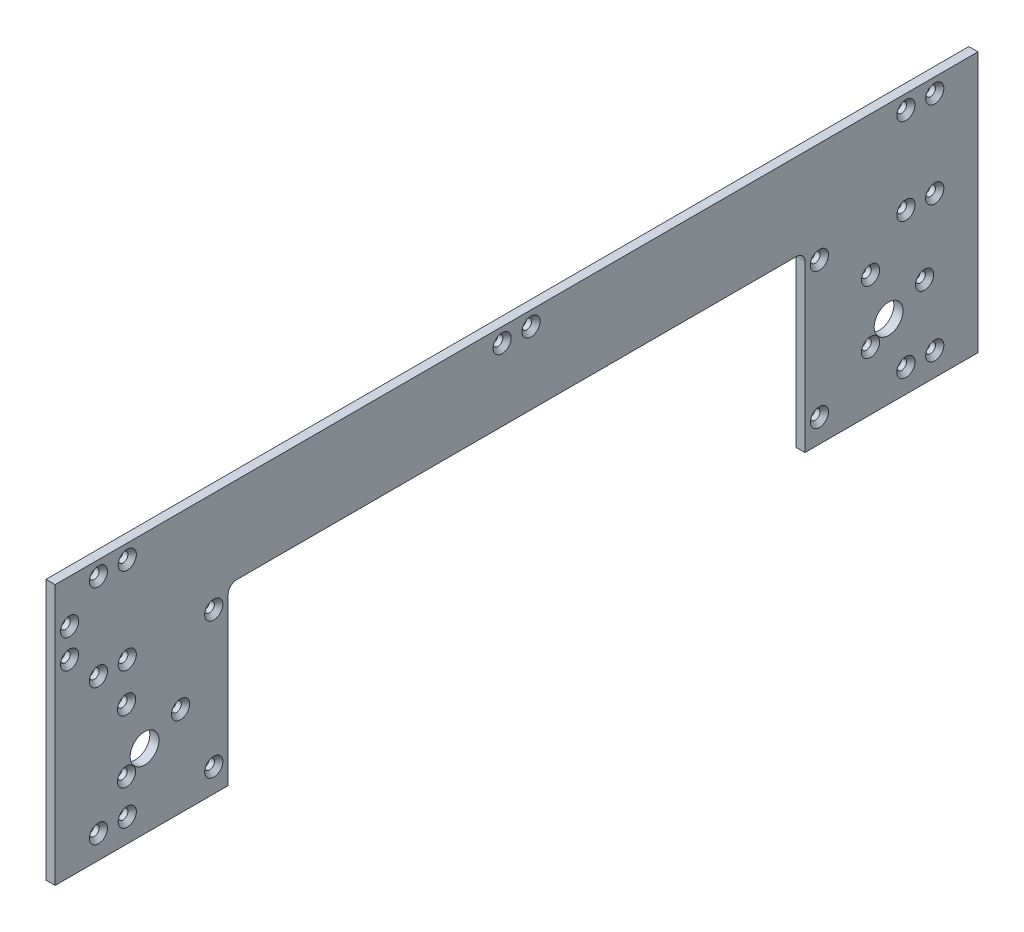
SolidWorks part; units mm, degrees
material "Garolite (G-10/FR4)"
ref_plane "Front Plane" through (0, 0, 0) normal (0, 0, 1) x (1, 0, 0)
ref_plane "Top Plane" through (0, 0, 0) normal (0, 1, 0) x (1, 0, 0)
ref_plane "Right Plane" through (0, 0, 0) normal (1, 0, 0) x (0, 0, -1)
sketch "Sketch1" plane through (0, 0, 0) normal (1, 0, 0) x (0, 0, -1)
  line L0 (160, 0) -> (160, 3.175)
  line L1 (-160, 0) -> (160, 0)
  line L2 (160, 3.175) -> (160, 47.175)
  line L3 (-160, 90.35) -> (160, 90.35)
  line L4 (-160, 3.175) -> (-160, 47.175)
  line L5 (-160, 3.175) -> (-160, 0)
  line L6 (160, 47.175) -> (160, 50.35)
  line L7 (160, 50.35) -> (160, 60.35)
  line L8 (160, 60.35) -> (160, 90.35)
  line L9 (-160, 47.175) -> (-160, 50.35)
  line L10 (-160, 50.35) -> (-160, 60.35)
  line L11 (-160, 60.35) -> (-160, 90.35)
  dimension "D1" = 320
  dimension "D2" = 30
  dimension "D3" = 3.175
  dimension "D4" = 44
  dimension "D5" = 3.175
  dimension "D6" = 10
extrude "Boss-Extrude1" add sketch "Sketch1" along normal blind 3.175
hole_wizard "CSK for M3 Flat Head Machine Screw1" positions "Sketch3" profile "Sketch2" countersink size "M3" standard "Ansi Metric" end condition through all
sketch "Sketch3" plane through (3.175, 0, 0) normal (1, 0, 0) x (0, 0, -1)
  line L0 (-105, 8.175) -> (-160, 8.175) construction
  line L1 (-160, 90.35) -> (-160, 0) construction
  line L3 (-160, 0) -> (160, 0) construction
  line L4 (-105, 55.35) -> (-160, 55.35) construction
  line L10 (-145, 8.175) -> (-145, 85.35) construction
  line L12 (-135, 8.175) -> (-135, 85.35) construction
  line L14 (-105, 8.175) -> (-105, 85.35) construction
  line L16 (-105, 85.35) -> (-160, 85.35) construction
  line L17 (-105, 85.35) -> (-5, 85.35) construction
  point P0 (-145, 8.175)
  point P1 (-135, 8.175)
  point P3 (-105, 8.175)
  point P15 (-145, 55.35)
  point P17 (-135, 55.35)
  point P19 (-105, 55.35)
  point P55 (-145, 85.35)
  point P57 (-135, 85.35)
  point P59 (-5, 85.35)
  dimension "D1" = 8.175
  dimension "D2" = 15
  dimension "D3" = 10
  dimension "D4" = 30
  dimension "D5" = 30
  dimension "D6" = 140
  dimension "D8" = 55.35
sketch "Sketch2" plane through (3.175, 8.175, 145) normal (0, 1, 0) x (0, 0, -1)
  line L0 (0, 0) -> (0, 3.175)
  line L1 (0, 3.175) -> (1.7, 3.175)
  line L2 (1.7, 3.175) -> (1.7, 1.45)
  line L3 (1.7, 1.45) -> (3.15, 0)
  line L5 (3.15, 0) -> (0, 0)
  line L6 (-1.7, 1.45) -> (-3.15, 0) construction
  line L11 (0, -6.35) -> (0, 107.95) construction
  dimension "Thru Hole Dia." = 3.4
  dimension "Thru Hole Depth" = 3.175
  dimension "Near C'Sink Dia." = 6.3
  dimension "Near C'Sink Angle" = 90
mirror "Mirror1" about plane through (0, 0, 0) normal (0, 0, 1) of "CSK for M3 Flat Head Machine Screw1"
sketch "Sketch4" plane through (3.175, 0, 0) normal (1, 0, 0) x (0, 0, -1)
  line L0 (-100, 57.35) -> (-100, 0)
  line L1 (-160, 0) -> (160, 0) construction
  line L2 (-160, 90.35) -> (-160, 0) construction
  line L3 (-97, 60.35) -> (97, 60.35)
  line L4 (0, 60.35) -> (0, 0) construction
  line L5 (100, 0) -> (-100, 0)
  line L6 (100, 57.35) -> (100, 0)
  line L7 (-129, 25.675) -> (129, 25.675) construction
  line L8 (160, 0) -> (160, 90.35) construction
  arc A0 (-100, 57.35) -> (-97, 60.35) centre (-97, 57.35) cw
  arc A1 (100, 57.35) -> (97, 60.35) centre (97, 57.35) ccw
  circle A2 centre (-129, 25.675) radius 5
  circle A3 centre (129, 25.675) radius 5
  dimension "D3" = 3
  dimension "D4" = 10
  dimension "D1" = 60
  dimension "D2" = 60.35
  dimension "D5" = 31
  dimension "D6" = 25.675
  dimension "D7" = 31
extrude "Cut-Extrude1" cut sketch "Sketch4" against normal through all
hole_wizard "CSK for M3 Flat Head Machine Screw2" positions "Sketch6" profile "Sketch5" countersink size "M3" standard "Ansi Metric" end condition through all
sketch "Sketch6" plane through (3.175, 0, 0) normal (1, 0, 0) x (0, 0, -1)
  line L0 (-155, 65.35) -> (-155, 90.35) construction
  line L1 (160, 90.35) -> (-160, 90.35) construction
  line L5 (-160, 90.35) -> (-160, 0) construction
  point P0 (-155, 65.35)
  point P1 (-155, 75.35)
  dimension "D1" = 10
  dimension "D2" = 5
  dimension "D3" = 15
sketch "Sketch5" plane through (3.175, 65.35, 155) normal (0, 1, 0) x (0, 0, -1)
  line L0 (0, 0) -> (0, 3.175)
  line L1 (0, 3.175) -> (1.7, 3.175)
  line L2 (1.7, 3.175) -> (1.7, 1.45)
  line L3 (1.7, 1.45) -> (3.15, 0)
  line L5 (3.15, 0) -> (0, 0)
  line L6 (-1.7, 1.45) -> (-3.15, 0) construction
  line L11 (0, -6.35) -> (0, 107.95) construction
  dimension "Thru Hole Dia." = 3.4
  dimension "Thru Hole Depth" = 3.175
  dimension "Near C'Sink Dia." = 6.3
  dimension "Near C'Sink Angle" = 90
hole_wizard "CSK for M3 Flat Head Machine Screw3" positions "Sketch8" profile "Sketch7" countersink size "M3" standard "Ansi Metric" end condition through all
sketch "Sketch8" plane through (3.175, 0, 0) normal (1, 0, 0) x (0, 0, -1)
  line L0 (-116.5, 31.175) -> (-129, 31.175) construction
  line L2 (-135.25, 20.3497) -> (-129, 31.175) construction
  line L3 (-129, 31.175) -> (-135.25, 42.0003) construction
  line L4 (-129, 31.175) -> (-129, 25.675) construction
  line L6 (-160, 0) -> (-100, 0) construction
  circle A0 centre (-129, 31.175) radius 12.5
  point P1 (-116.5, 31.175)
  point P26 (-135.25, 20.3497)
  point P28 (-135.25, 42.0003)
  dimension "D1" = 25
  dimension "D2" = 120
  dimension "D3" = 120
  dimension "D4" = 31.175
sketch "Sketch7" plane through (3.175, 31.175, 116.5) normal (0, 1, 0) x (0, 0, -1)
  line L0 (0, 0) -> (0, 3.175)
  line L1 (0, 3.175) -> (1.7, 3.175)
  line L2 (1.7, 3.175) -> (1.7, 1.45)
  line L3 (1.7, 1.45) -> (3.15, 0)
  line L5 (3.15, 0) -> (0, 0)
  line L6 (-1.7, 1.45) -> (-3.15, 0) construction
  line L11 (0, -6.35) -> (0, 107.95) construction
  dimension "Thru Hole Dia." = 3.4
  dimension "Thru Hole Depth" = 3.175
  dimension "Near C'Sink Dia." = 6.3
  dimension "Near C'Sink Angle" = 90
pattern_linear "LPattern1" count 2 spacing 258 along (0, 0, -1) of "CSK for M3 Flat Head Machine Screw3"
